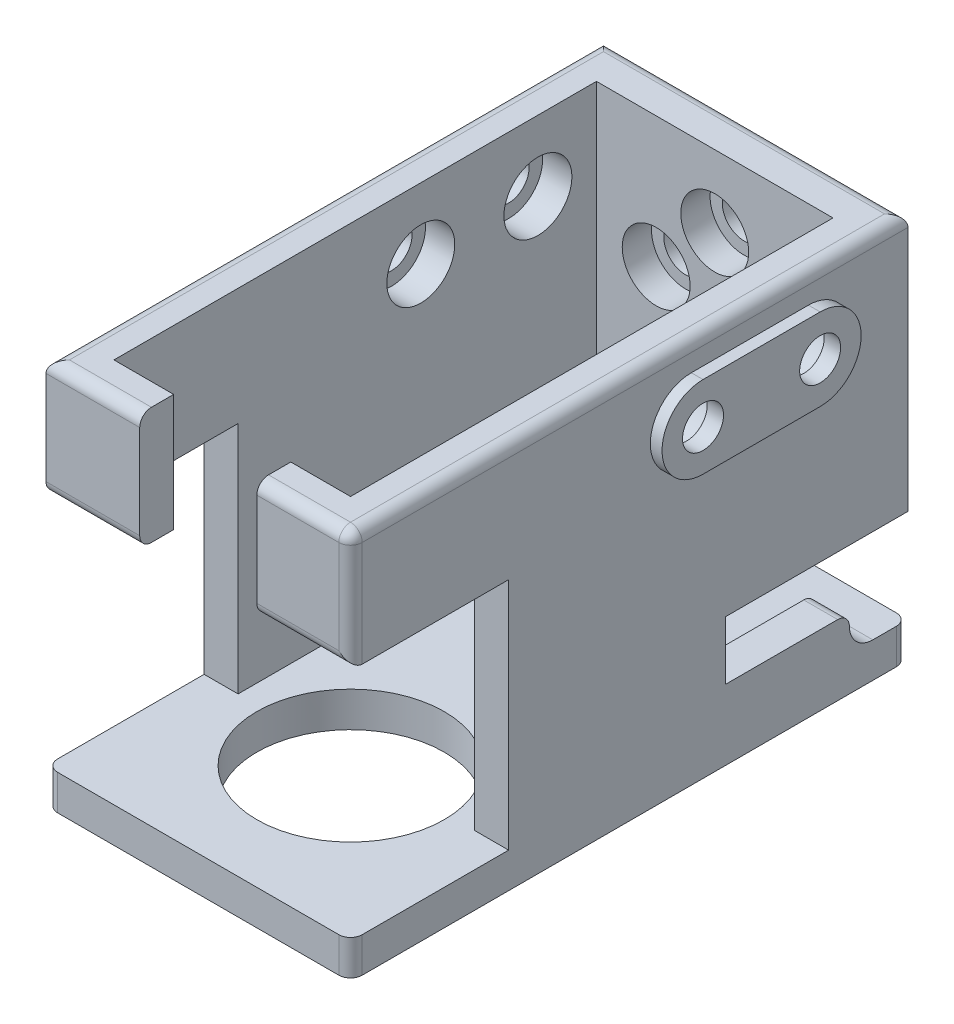
SolidWorks part; units mm, degrees
ref_plane "Front Plane" through (0, 0, 0) normal (0, 0, 1) x (1, 0, 0)
ref_plane "Top Plane" through (0, 0, 0) normal (0, 1, 0) x (1, 0, 0)
ref_plane "Right Plane" through (0, 0, 0) normal (1, 0, 0) x (0, 0, -1)
sketch "Sketch1" plane through (0, 0, 0) normal (0, 1, 0) x (1, 0, 0)
  line L0 (5, -23.5) -> (13, -23.5)
  line L1 (-10, 20.5) -> (10, 20.5)
  line L2 (-10, 20.5) -> (-10, -20.5)
  line L3 (-10, -20.5) -> (-5, -20.5)
  line L4 (10, 20.5) -> (10, -20.5)
  line L5 (-10, 20.5) -> (10, -20.5) construction
  line L6 (-10, -20.5) -> (10, 20.5) construction
  line L7 (-13, 23.5) -> (13, 23.5)
  line L8 (-13, 23.5) -> (-13, -23.5)
  line L9 (-13, -23.5) -> (-5, -23.5)
  line L10 (13, 23.5) -> (13, -23.5)
  line L11 (-13, 23.5) -> (13, -23.5) construction
  line L12 (-13, -23.5) -> (13, 23.5) construction
  line L14 (-5, -20.5) -> (-5, -23.5)
  line L16 (5, -20.5) -> (5, -23.5)
  line L17 (5, -20.5) -> (10, -20.5)
  point P0 (0, 0)
  point P6 (0, 0)
  dimension "D1" = 20
  dimension "D2" = 41
  dimension "D3" = 3
  dimension "D4" = 3
  dimension "D5" = 5
  dimension "D6" = 5
extrude "Boss-Extrude1" add sketch "Sketch1" along normal blind 10
sketch "Sketch2" plane through (13, 0, 0) normal (1, 0, 0) x (0, 0, -1)
  line L0 (-23.5, 0) -> (23.5, 0) construction
  line L1 (-10, 0) -> (10, 0)
  line L2 (-10, 0) -> (-10, -17)
  line L3 (-10, -17) -> (10, -17)
  line L4 (10, 0) -> (10, -17)
  dimension "D1" = 10
  dimension "D2" = 10
  dimension "D3" = 17
extrude "Boss-Extrude2" add sketch "Sketch2" against normal blind 3
ref_plane "Plane1" through (0, 0, 0) normal (1, 0, 0) x (0, 0, -1)
mirror "Mirror1" about plane through (0, 0, 0) normal (1, 0, 0) of "Boss-Extrude2"
sketch "Sketch3" plane through (0, -17, 0) normal (0, -1, 0) x (1, 0, 0)
  line L1 (-13, 23.5) -> (13, 23.5)
  line L2 (-13, 23.5) -> (-13, -23.5)
  line L3 (-13, -23.5) -> (13, -23.5)
  line L4 (13, 23.5) -> (13, -23.5)
extrude "Boss-Extrude3" add sketch "Sketch3" along normal blind 3
sketch "Sketch5" plane through (0, -20, 0) normal (0, -1, 0) x (1, 0, 0)
  line L1 (10, 20.5) -> (5, 20.5) construction
  line L2 (10, 10) -> (10, -10) construction
  line L3 (-10, 10) -> (-10, -10) construction
  line L4 (-8, -4.5) -> (8, -4.5)
  line L5 (-8, -4.5) -> (-8, -8.5)
  line L6 (-8, -8.5) -> (8, -8.5)
  line L7 (8, -4.5) -> (8, -8.5)
  line L8 (-8, -12.5) -> (8, -12.5)
  line L9 (-8, -12.5) -> (-8, -16.5)
  line L10 (-8, -16.5) -> (8, -16.5)
  line L11 (8, -12.5) -> (8, -16.5)
  line L12 (-10, -10) -> (-10, -20.5) construction
  line L13 (10, -20.5) -> (10, -10) construction
  line L14 (-10, -20.5) -> (10, -20.5) construction
  circle A0 centre (0, 10.5) radius 8
  dimension "D1" = 10
  dimension "D2" = 10
  dimension "D3" = 2
  dimension "D4" = 2
  dimension "D5" = 2
  dimension "D6" = 2
  dimension "D7" = 4
  dimension "D8" = 4
  dimension "D9" = 4
  dimension "D10" = 4
extrude "Cut-Extrude1" cut sketch "Sketch5" against normal through all
sketch "Sketch6" plane through (13, 0, 0) normal (1, 0, 0) x (0, 0, -1)
  line L0 (23.5, -20) -> (23.5, 20.7) construction
  line L1 (23.5, -20) -> (-23.5422, -20) construction
  line L2 (23.5, -20) -> (23.5, 20.7) construction
  line L3 (23.5, 20.7) -> (-23.5422, 20.7) construction
  line L4 (-23.5422, -20) -> (-23.5422, 20.7) construction
  line L5 (23.5, -20) -> (23.5, 20.7) construction
  line L6 (23.5, 0.35) -> (-23.5422, 0.35) construction
  line L7 (10, -17) -> (10, 0) construction
  line L8 (23.5, 4.35) -> (29.5, 4.35)
  line L9 (23.5, 4.35) -> (23.5, -3.65)
  line L10 (23.5, -3.65) -> (29.5, -3.65)
  line L11 (29.5, 4.35) -> (29.5, -3.65)
  line L12 (23.5, 0) -> (10, 0)
  line L13 (23.5, 0) -> (23.5, -9.3)
  line L14 (23.5, -9.3) -> (10, -9.3)
  line L15 (10, 0) -> (10, -9.3)
  line M19 (10, -17) -> (10, 0)
  line M20 (10, 0) -> (23.5, 0)
  line M21 (23.5, 0) -> (23.5, 10)
  dimension "D1" = 40.7
  dimension "D2" = 4
  dimension "D3" = 4
  dimension "D4" = 6
  dimension "D5" = 5.65
extrude "Boss-Extrude4" add sketch "Sketch6" against normal blind 26 contours L11 L8 L9 L10 M21 | L14 L13 L9 M20 M19 region at (13, 0.35, -26.5) region at (13, -4.65, -16.75)
sketch "Sketch7" plane through (0, 0, 0) normal (0, 1, 0) x (1, 0, 0)
  line L1 (-10, 20.5) -> (10, 20.5)
  line L2 (-10, 20.5) -> (-10, 10)
  line L3 (-10, 10) -> (10, 10)
  line L4 (10, 20.5) -> (10, 10)
extrude "Cut-Extrude2" cut sketch "Sketch7" against normal blind 10
sketch "Sketch9" plane through (0, 4.35, 0) normal (0, 1, 0) x (1, 0, 0)
  line L0 (13, 23.5) -> (-13, 23.5) construction
  line L1 (-13, 29.5) -> (-5, 29.5)
  line L2 (-13, 29.5) -> (-13, 23.5)
  line L3 (-13, 23.5) -> (-5, 23.5)
  line L4 (-5, 29.5) -> (-5, 23.5)
  line L5 (-13, 23.5) -> (13, 23.5) construction
  line L6 (13, 29.5) -> (5, 29.5)
  line L7 (13, 29.5) -> (13, 23.5)
  line L8 (13, 23.5) -> (5, 23.5)
  line L9 (5, 29.5) -> (5, 23.5)
  dimension "D1" = 8
  dimension "D2" = 8
extrude "Cut-Extrude3" cut sketch "Sketch9" against normal blind 10
sketch "Sketch10" plane through (0, 0, -29.5) normal (0, 0, -1) x (-1, 0, 0)
  line L1 (-15, 15) -> (15, 15)
  line L2 (-15, 15) -> (-15, -15)
  line L3 (-15, -15) -> (15, -15)
  line L4 (15, 15) -> (15, -15)
  line L5 (-15, 15) -> (15, -15) construction
  line L6 (-15, -15) -> (15, 15) construction
  point P0 (0, 0)
  dimension "D1" = 30
  dimension "D2" = 30
extrude "Boss-Extrude5" add sketch "Sketch10" along normal blind 3
sketch "Sketch11" plane through (0, 0, -32.5) normal (0, 0, -1) x (-1, 0, 0)
  circle A0 centre (0, 10) radius 1.75
  circle A4 centre (10, 0) radius 1.75
  circle A5 centre (0, -10) radius 1.75
  circle A6 centre (-10, 0) radius 1.75
  point P12 (-1, 1)
  point P13 (0, 0)
  dimension "D1" = 3.5
  dimension "D3" = 0
  dimension "D4" = 4
  dimension "D5" = 10
  dimension "D6" = 10
  dimension "D2" = 10
extrude "Cut-Extrude4" cut sketch "Sketch11" against normal blind 5
sketch "Sketch12" plane through (0, -20, 0) normal (0, -1, 0) x (1, 0, 0)
  line L9 (-13, 23.5) -> (13, 23.5)
  line L10 (-13, 23.5) -> (-13, -23.5)
  line L11 (-13, -23.5) -> (13, -23.5)
  line L12 (13, 23.5) -> (13, -23.5)
  circle A0 centre (0, 10.5) radius 8
extrude "Boss-Extrude6" add sketch "Sketch12" along normal blind 3
sketch "Sketch14" plane through (0, -17, 0) normal (0, 1, 0) x (1, 0, 0)
  line L1 (-13, 23.5) -> (13, 23.5)
  line L2 (-13, 23.5) -> (-13, -23.5)
  line L3 (-13, -23.5) -> (13, -23.5)
  line L4 (13, 23.5) -> (13, -23.5)
  line L5 (-13, 10) -> (-10, 10)
  line L6 (-13, 10) -> (-13, -10)
  line L7 (-13, -10) -> (-10, -10)
  line L8 (-10, 10) -> (-10, -10)
  line L9 (10, -10) -> (13, -10)
  line L10 (10, -10) -> (10, 10)
  line L11 (10, 10) -> (13, 10)
  line L12 (13, -10) -> (13, 10)
  circle M1 centre (0, -10.5) radius 8
  line M2 (8, 4.5) -> (-8, 4.5)
  line M3 (-8, 4.5) -> (-8, 8.5)
  line M4 (-8, 8.5) -> (8, 8.5)
  line M5 (8, 8.5) -> (8, 4.5)
  line M6 (8, 12.5) -> (-8, 12.5)
  line M7 (-8, 12.5) -> (-8, 16.5)
  line M8 (-8, 16.5) -> (8, 16.5)
  line M9 (8, 16.5) -> (8, 12.5)
  line M10 (13, -10) -> (10, -10)
  line M11 (10, -10) -> (10, 10)
  line M12 (10, 10) -> (13, 10)
  line M13 (13, 10) -> (13, 23.5)
  line M14 (13, 23.5) -> (-13, 23.5)
  line M15 (-13, 23.5) -> (-13, 10)
  line M16 (-13, 10) -> (-10, 10)
  line M17 (-10, 10) -> (-10, -10)
  line M18 (-10, -10) -> (-13, -10)
  line M19 (-13, -10) -> (-13, -23.5)
  line M20 (-13, -23.5) -> (13, -23.5)
  line M21 (13, -23.5) -> (13, -10)
extrude "Cut-Extrude5" cut sketch "Sketch14" against normal blind 3 contours M21 M10 M11 M12 M13 M14 M15 M16 M17 M18 M19 M20 M5 M2 M3 M4 M9 M6 M7 M8 M1 region at (0, -17, -0.9925)
sketch "Sketch15" plane through (13, 0, 0) normal (1, 0, 0) x (0, 0, -1)
  line L0 (10, -20) -> (23.5, -20) construction
  line L1 (23.5, -17) -> (-23.5, -17)
  line L2 (23.5, -17) -> (23.5, 20.7)
  line L3 (23.5, 20.7) -> (-23.5, 20.7)
  line L4 (-23.5, -17) -> (-23.5, 20.7)
  line L5 (23.5, -23) -> (-23.5, -23) construction
  line L6 (11.2985, 20.7) -> (11.2985, -23) construction
  line L7 (11.2985, -23) -> (11.2985, -1.15) construction
  line L8 (11.2985, -1.15) -> (42.746, -1.15) construction
  line L10 (32.5, 15) -> (23.5, 15)
  line L11 (32.5, 15) -> (32.5, -15.2438)
  line L12 (32.5, -15.2438) -> (23.5, -15.2438)
  line L13 (23.5, 15) -> (23.5, -15.2438)
  line M11 (23.5, -9.3) -> (23.5, 10)
  dimension "D1" = 3
  dimension "D2" = 43.7
extrude "Cut-Extrude7" cut sketch "Sketch15" against normal through all both and the other way through all contours L12 L11 L10 L2 M11 region at (13, -0.1219, -28)
sketch "Sketch16" plane through (0, -9.3, 0) normal (0, -1, 0) x (1, 0, 0)
  line L0 (-13, 23.5) -> (-13, -23.5) construction
  line L1 (13, -23.5) -> (-13, -23.5)
  line L2 (13, -23.5) -> (13, -10)
  line L3 (13, -10) -> (-13, -10)
  line L4 (-13, -23.5) -> (-13, -10)
  line L5 (10, -10) -> (13, -10) construction
  line L7 (10, -20.5) -> (-10, -20.5)
  line L8 (10, -20.5) -> (10, -10)
  line L9 (10, -10) -> (-10, -10)
  line L10 (-10, -20.5) -> (-10, -10)
  line M2 (10, -20.5) -> (-10, -20.5)
  line M3 (-10, -20.5) -> (-10, -10)
  line M4 (-10, -10) -> (-13, -10)
  line M5 (-13, -10) -> (-13, -23.5)
  line M6 (-13, -23.5) -> (13, -23.5)
  line M7 (13, -23.5) -> (13, -10)
  line M8 (13, -10) -> (10, -10)
  line M9 (10, -10) -> (10, -20.5)
  dimension "D1" = 0
extrude "Boss-Extrude7" add sketch "Sketch16" along normal blind 10.7 contours M9 M2 M3 M4 M5 M6 M7 M8 region at (0, -9.3, -23.207)
sketch "Sketch18" plane through (13, 0, 0) normal (1, 0, 0) x (0, 0, -1)
  line L0 (23.5, 10) -> (23.5, -23) construction
  line L1 (23.5, -17) -> (8.5, -17)
  line L2 (23.5, -17) -> (23.5, -12)
  line L3 (23.5, -12) -> (8.5, -12)
  line L4 (8.5, -17) -> (8.5, -12)
  line L5 (-23.5, -20) -> (-10, -20) construction
  dimension "D1" = 3
  dimension "D2" = 15
  dimension "D3" = 5
extrude "Cut-Extrude8" cut sketch "Sketch18" against normal blind 10
mirror "Mirror2" about plane through (0, 0, 0) normal (1, 0, 0) of "Cut-Extrude8"
sketch "Sketch21" plane through (0, 0, -23.5) normal (0, 0, -1) x (-1, 0, 0)
  line L0 (0, 20.7) -> (0, -23) construction
  line L1 (-13, -23) -> (13, -23)
  line L2 (-13, -23) -> (-13, 20.7)
  line L3 (-13, 20.7) -> (13, 20.7)
  line L4 (13, -23) -> (13, 20.7)
  line L5 (0, -23) -> (0, -1.15) construction
  line L6 (0, -1.15) -> (13, -1.15) construction
  circle A0 centre (0, 3.85) radius 1.85
  circle A1 centre (5, -1.15) radius 1.85
  circle A2 centre (0, -6.15) radius 1.85
  circle A3 centre (-5, -1.15) radius 1.85
  point P19 (0, -1.15)
  dimension "D2" = 5
  dimension "D3" = 3.7
  dimension "D5" = 5
  dimension "D6" = 5
  dimension "D1" = 43.7
  dimension "D4" = 4
extrude "Cut-Extrude9" cut sketch "Sketch21" against normal blind 5 contours A3 | A0 | A1 | A2 region at (0, 3.85, -23.5) region at (-5, -1.15, -23.5) region at (0, -6.15, -23.5) region at (5, -1.15, -23.5)
sketch "Sketch22" plane through (0, 0, -20.5) normal (0, 0, 1) x (1, 0, 0)
  line L0 (0, 3.85) -> (0, -6.15) construction
  line L1 (0, -6.15) -> (0, -1.15) construction
  line L2 (0, -1.15) -> (5, -1.15) construction
  circle A0 centre (0, 3.85) radius 2.9
  circle A1 centre (5, -1.15) radius 2.9
  circle A2 centre (0, -6.15) radius 2.9
  circle A3 centre (-5, -1.15) radius 2.9
  point P17 (0, -1.15)
  dimension "D1" = 5.8
  dimension "D2" = 4
extrude "Cut-Extrude10" cut sketch "Sketch22" against normal blind 2.6
sketch "Sketch23" plane through (0, 0, -23.5) normal (0, 0, -1) x (-1, 0, 0)
  line L0 (-3, -17) -> (-13, -17)
  line L1 (-13, 10) -> (13, 10)
  line L2 (-13, 10) -> (-13, -12)
  line L3 (-13, -12) -> (-3, -12)
  line L4 (13, 10) -> (13, -12)
  line L10 (-3, -12) -> (-3, -17)
  line L12 (3, -12) -> (3, -17)
  line L13 (13, -17) -> (3, -17)
  line L14 (13, -17) -> (13, -23)
  line L15 (13, -23) -> (-13, -23)
  line L16 (-13, -17) -> (-13, -23)
  line L17 (3, -12) -> (13, -12)
  circle A0 centre (0, 3.85) radius 1.75
  circle A1 centre (0, -6.15) radius 1.75
  circle A2 centre (5, -1.15) radius 1.75
  circle A3 centre (-5, -1.15) radius 1.75
  circle M1 centre (-5, -1.15) radius 1.85
  circle M2 centre (0, 3.85) radius 1.85
  circle M3 centre (5, -1.15) radius 1.85
  circle M4 centre (0, -6.15) radius 1.85
  line M5 (3, -12) -> (13, -12)
  line M6 (13, -12) -> (13, 10)
  line M7 (13, 10) -> (-13, 10)
  line M8 (-13, 10) -> (-13, -12)
  line M9 (-13, -12) -> (-3, -12)
extrude "Boss-Extrude11" add sketch "Sketch23" along normal blind 0.6 contours L3 M9 M5 M6 M7 M8 M2 M4 M3 M1 region at (2.5799, -14.5, -23.5)
sketch "Sketch24" plane through (0, 0, -24.1) normal (0, 0, -1) x (-1, 0, 0)
  line L5 (5, -1.15) -> (0, -1.15) construction
  line L7 (0, 3.85) -> (0, -6.15) construction
  line L8 (-4.5, 6.35) -> (4.5, 6.35)
  line L9 (-13, 6.35) -> (-13, -8.65)
  line L10 (-4.5, -8.65) -> (4.5, -8.65)
  line L11 (13, 6.35) -> (13, -8.65)
  line L12 (-13, 6.35) -> (13, -8.65) construction
  line L13 (-13, -8.65) -> (13, 6.35) construction
  line L15 (-7.5, 6.35) -> (7.5, 6.35)
  line L16 (-7.5, 3.35) -> (-7.5, -5.65)
  line L17 (-7.5, -8.65) -> (7.5, -8.65)
  line L18 (7.5, 3.35) -> (7.5, -5.65)
  line L19 (-7.5, 6.35) -> (7.5, -8.65) construction
  line L20 (-7.5, -8.65) -> (7.5, 6.35) construction
  circle A0 centre (0, 3.85) radius 1.75
  circle A1 centre (0, -6.15) radius 1.75
  circle A2 centre (5, -1.15) radius 1.75
  circle A3 centre (-5, -1.15) radius 1.75
  arc A4 (7.5, 3.35) -> (4.5, 6.35) centre (4.5, 3.35) ccw
  arc A5 (7.5, -5.65) -> (4.5, -8.65) centre (4.5, -5.65) cw
  arc A6 (-4.5, -8.65) -> (-7.5, -5.65) centre (-4.5, -5.65) cw
  arc A7 (-7.5, 3.35) -> (-4.5, 6.35) centre (-4.5, 3.35) cw
  point P0 (0, -0.7463)
  circle M11 centre (0, 3.85) radius 1.85
  circle M12 centre (0, -6.15) radius 1.85
  circle M25 centre (5, -1.15) radius 1.85
  circle M26 centre (-5, -1.15) radius 1.85
  dimension "D3" = 3
  dimension "D2" = 15
extrude "Boss-Extrude12" add sketch "Sketch24" along normal blind 4 contours A7 L16 A6 L10 A5 L18 A4 L8 M12 M25 M26 M11 region at (0, -1.15, -24.1)
sketch "Sketch25" plane through (0, 0, -24.1) normal (0, 0, -1) x (-1, 0, 0)
  line L1 (-10, -17) -> (-3, -17)
  line L2 (-10, -17) -> (-10, -20)
  line L3 (-10, -20) -> (-3, -20)
  line L4 (-3, -17) -> (-3, -20)
  line L5 (3, -17) -> (10, -17)
  line L6 (3, -17) -> (3, -20)
  line L7 (3, -20) -> (10, -20)
  line L8 (10, -17) -> (10, -20)
  dimension "D1" = 3
  dimension "D2" = 3
extrude "Cut-Extrude11" cut sketch "Sketch25" against normal blind 5
sketch "Sketch26" plane through (0, 10, 0) normal (0, 1, 0) x (1, 0, 0)
  line L0 (-10, 20.5) -> (10, 20.5) construction
  line L1 (-10.1, 20.6) -> (10.1, 20.6)
  line L2 (-10.1, 20.6) -> (-10.1, -20.6)
  line L3 (-10.1, -20.6) -> (10.1, -20.6)
  line L4 (10.1, 20.6) -> (10.1, -20.6)
  line L5 (-10, -20.5) -> (-10, 20.5) construction
  line L6 (10, -10) -> (10, 24.1) construction
  line L7 (-5, -20.5) -> (-10, -20.5) construction
  dimension "D1" = 0.1
  dimension "D2" = 0.1
  dimension "D3" = 0.1
  dimension "D4" = 0.1
extrude "Cut-Extrude12" cut sketch "Sketch26" against normal blind 30
sketch "Sketch27" plane through (0, 0, -24.1) normal (0, 0, -1) x (-1, 0, 0)
  line L0 (0, -23) -> (0, -16.7281) construction
  line L1 (-13, -23) -> (13, -23) construction
  line L2 (-10, -20) -> (-10.1, -20)
  line L3 (10, -17) -> (10.1, -17)
  line L4 (10, -17) -> (10, -20)
  line L5 (10, -20) -> (10.1, -20)
  line L6 (10.1, -17) -> (10.1, -20)
  line L7 (-10.1, -17) -> (-10.1, -20)
  line L8 (-10, -17) -> (-10.1, -17)
  line L9 (-10, -17) -> (-10, -20)
extrude "Cut-Extrude13" cut sketch "Sketch27" against normal through all
sketch "Sketch28" plane through (0, -23, 0) normal (0, -1, 0) x (1, 0, 0)
  line L0 (0, 10.5) -> (0, 23.5) construction
  line L1 (13, 23.5) -> (-13, 23.5) construction
  line L2 (0, -24.1) -> (0, -11.1) construction
  line L3 (4.5, -24.1) -> (-4.5, -24.1) construction
  line L4 (0, 10.5) -> (0, -11.1) construction
  circle A0 centre (0, -11.1) radius 8
  dimension "D2" = 16
  dimension "D1" = 13
extrude "Cut-Extrude14" cut sketch "Sketch28" against normal through all
sketch "Sketch29" plane through (0, 0, -24.1) normal (0, 0, -1) x (-1, 0, 0)
  line L0 (-13, -17) -> (-13, -23) construction
  line L1 (-10.1, -17) -> (-13, -17)
  line L2 (-10.1, -17) -> (-10.1, -20)
  line L3 (-10.1, -20) -> (-13, -20)
  line L4 (-13, -17) -> (-13, -20)
  line L6 (10.1, -20) -> (13, -20)
  line L7 (10.1, -20) -> (10.1, -17)
  line L8 (10.1, -17) -> (13, -17)
  line L9 (13, -20) -> (13, -17)
extrude "Cut-Extrude15" cut sketch "Sketch29" against normal blind 5
fillet "Fillet1" radius 2 2 edges at (-3, -20, -22.35) (3, -20, -22.35)
fillet "Fillet2" radius 2 2 edges at (-11.55, -20, -19.1) (11.55, -20, -19.1)
fillet "Fillet3" radius 1 14 edges at (-11.55, -17, -19.1) (11.55, -17, -19.1) (-13, -21.5, -24.1) (13, -21.5, -24.1) (-13, -21.5, 23.5) (13, -21.5, 23.5) (0, 10, -24.1) (-13, 10, -0.3) (-9, 0, 23.5) (-9, 10, 23.5) (9, 0, 23.5) (9, 10, 23.5) (13, 10, -0.3) (13, 5, 23.5)
sketch "Sketch30" plane through (-13, 0, 0) normal (-1, 0, 0) x (0, 0, 1)
  line L0 (-24.1, -12) -> (-24.1, 9) construction
  line L1 (-28.9275, 7.7667) -> (-24.1, 7.7667)
  line L2 (-28.9275, 7.7667) -> (-28.9275, -11.0519)
  line L3 (-28.9275, -11.0519) -> (-24.1, -11.0519)
  line L4 (-24.1, 7.7667) -> (-24.1, -11.0519)
extrude "Cut-Extrude16" cut sketch "Sketch30" against normal through all
sketch "Sketch31" plane through (-13, 0, 0) normal (-1, 0, 0) x (0, 0, 1)
  line L0 (-20.6, -12) -> (-20.6, 10) construction
  line L1 (23.5, 9) -> (-24.1, 9) construction
  circle A0 centre (-15.6, 4) radius 1.75
  circle A1 centre (-5.6, 4) radius 1.75
  dimension "D1" = 3.5
  dimension "D2" = 5
  dimension "D3" = 5
  dimension "D5" = 10
  dimension "D4" = 2
extrude "Cut-Extrude17" cut sketch "Sketch31" against normal through all
sketch "Sketch32" plane through (10.1, 0, 0) normal (-1, 0, 0) x (0, 0, 1)
  circle A0 centre (-15.6, 4) radius 2.9
  circle A1 centre (-5.6, 4) radius 2.9
  dimension "D1" = 5.8
  dimension "D2" = 2
extrude "Cut-Extrude18" cut sketch "Sketch32" against normal blind 2.5
sketch "Sketch33" plane through (13, 0, 0) normal (1, 0, 0) x (0, 0, -1)
  line L1 (5.6, 7.5) -> (15.6, 7.5)
  line L3 (5.6, 0.5) -> (15.6, 0.5)
  arc A0 (5.6, 7.5) -> (5.6, 0.5) centre (5.6, 4) ccw
  arc A1 (15.6, 0.5) -> (15.6, 7.5) centre (15.6, 4) ccw
  circle A2 centre (5.6, 4) radius 1.75
  circle A3 centre (15.6, 4) radius 1.75
  dimension "D1" = 7
  dimension "D2" = 7
extrude "Boss-Extrude13" add sketch "Sketch33" along normal blind 1
mirror "Mirror3" about plane through (0, 0, 0) normal (1, 0, 0) of "Boss-Extrude13"
mirror "Mirror4" about plane through (0, 0, 0) normal (1, 0, 0) of "Cut-Extrude18"
sketch "Sketch34" plane through (0, -20, 0) normal (0, 1, 0) x (1, 0, 0)
  circle A0 centre (0, 11.1) radius 8
  circle A1 centre (0, 11.1) radius 4
  dimension "D1" = 8
extrude "Boss-Extrude14" add sketch "Sketch34" against normal blind 1
sketch "Sketch35" plane through (0, -23, 0) normal (0, -1, 0) x (1, 0, 0)
  line L0 (12, -24.1) -> (-12, -24.1) construction
  line L2 (-3.5, -18.2937) -> (-3.5, -24.1)
  line L3 (-3.5, -24.1) -> (3.5, -24.1)
  line L4 (3.5, -18.2937) -> (3.5, -24.1)
  line L5 (-6.5, -15.7637) -> (-6.5, -24.1)
  line L7 (6.5, -15.7637) -> (6.5, -24.1)
  line L9 (-6.5, -8.1) -> (-6.5, -27.1) construction
  line L10 (-6.5, -8.1) -> (6.5, -8.1) construction
  line L11 (6.5, -8.1) -> (6.5, -27.1) construction
  line L12 (3.5, -11.1) -> (3.5, -24.1) construction
  line L13 (-3.5, -11.1) -> (-3.5, -24.1) construction
  line L14 (-3.5, -11.1) -> (3.5, -11.1) construction
  line L15 (6.5, -24.1) -> (-6.5, -24.1)
  line L17 (-6.5, -27.1) -> (6.5, -27.1) construction
  circle A0 centre (0, -11.1) radius 3.5
  arc A1 (-6.5, -15.7637) -> (-3.5, -18.2937) centre (0, -11.1) ccw
  arc A2 (3.5, -18.2937) -> (6.5, -15.7637) centre (0, -11.1) ccw
  circle M1 centre (0, -11.1) radius 8
  line M4 (-12, -24.1) -> (12, -24.1)
  dimension "D1" = 7
  dimension "D2" = 3
extrude "Boss-Extrude15" add sketch "Sketch35" along normal blind 2 contours L7 L4 M1 M4 | L5 L2 M1 M4 region at (-5.0903, -23, -20.6334) region at (5.0903, -23, -20.6334)
